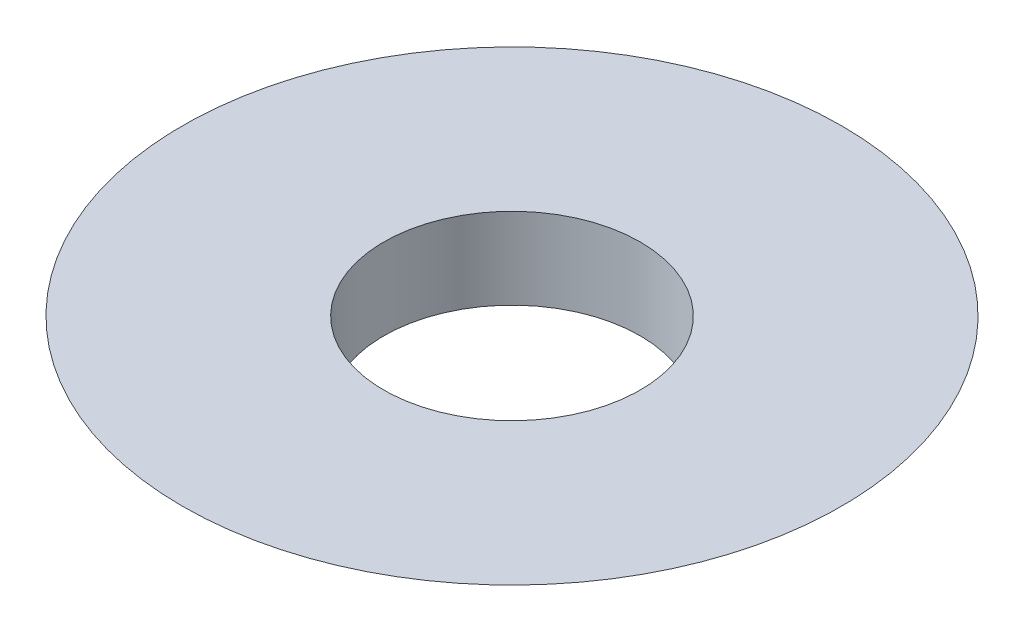
SolidWorks part; units mm, degrees
ref_plane "Front Plane" through (0, 0, 0) normal (0, 0, 1) x (1, 0, 0)
ref_plane "Top Plane" through (0, 0, 0) normal (0, 1, 0) x (1, 0, 0)
ref_plane "Right Plane" through (0, 0, 0) normal (1, 0, 0) x (0, 0, -1)
sketch "Sketch1" plane through (0, 0, 0) normal (0, 0, 1) x (1, 0, 0)
  line L0 (0, 0) -> (0, 50.2347) construction
  line L2 (16.51, 0) -> (42.4155, 10.4665)
  line L3 (42.4155, 10.4665) -> (16.51, 10.4665)
  line L4 (16.51, 10.4665) -> (16.51, 0)
  point P4 (42.4155, 9.9664)
  point P7 (0, 0)
  dimension "D1" = 33.02
  dimension "D2" = 68
  dimension "D3" = 27.94
revolve "Revolve1" add sketch "Sketch1" angle 360 about L0
